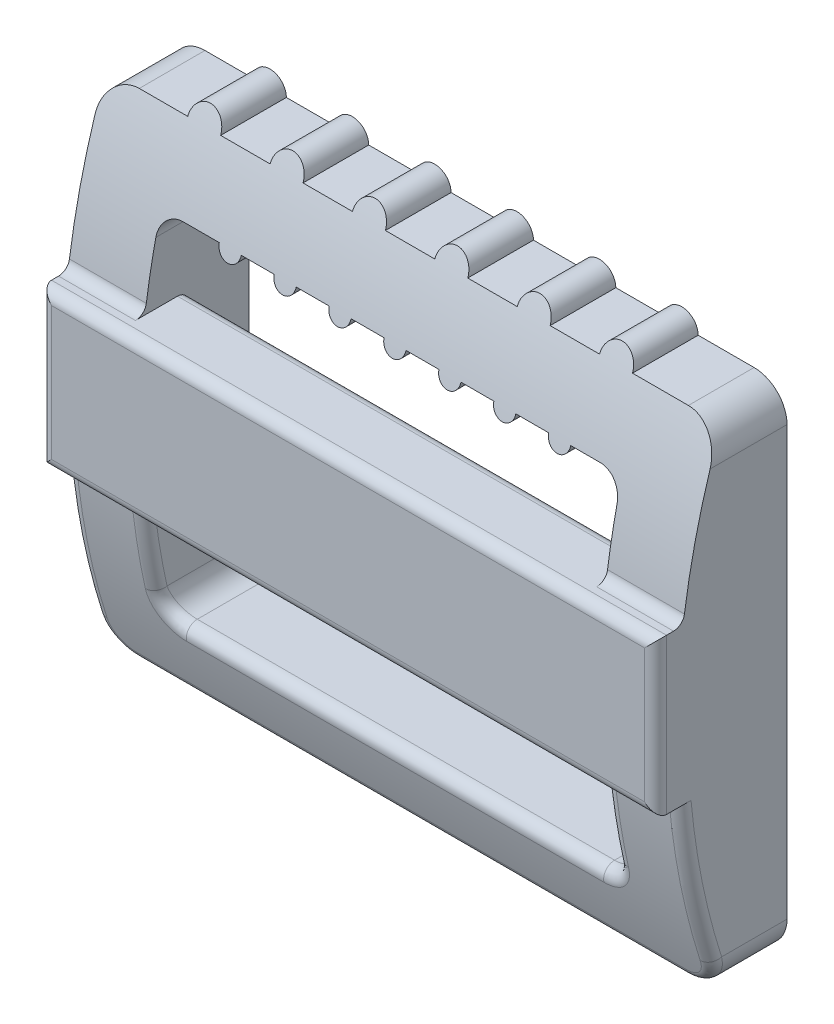
SolidWorks part; units mm, degrees
material "ABS"
ref_plane "Front Plane" through (0, 0, 0) normal (0, 0, 1) x (1, 0, 0)
ref_plane "Top Plane" through (0, 0, 0) normal (0, 1, 0) x (1, 0, 0)
ref_plane "Right Plane" through (0, 0, 0) normal (1, 0, 0) x (0, 0, -1)
sketch "Sketch1" plane through (0, 0, 0) normal (0, 0, 1) x (1, 0, 0)
  line L1 (-25, 22.5) -> (25, 22.5)
  line L2 (-28, 19.5) -> (-28, -19.5)
  line L3 (-25, -22.5) -> (25, -22.5)
  line L4 (28, 19.5) -> (28, -19.5)
  line L5 (-28, 22.5) -> (28, -22.5) construction
  line L6 (-28, -22.5) -> (28, 22.5) construction
  line L7 (-19, 16) -> (19, 16)
  line L8 (-21, 14) -> (-21, -14)
  line L9 (-19, -16) -> (19, -16)
  line L10 (21, 14) -> (21, -14)
  line L11 (-21, 16) -> (21, -16) construction
  line L12 (-21, -16) -> (21, 16) construction
  arc A0 (-28, -19.5) -> (-25, -22.5) centre (-25, -19.5) ccw
  arc A1 (25, -22.5) -> (28, -19.5) centre (25, -19.5) ccw
  arc A2 (25, 22.5) -> (28, 19.5) centre (25, 19.5) cw
  arc A3 (-25, 22.5) -> (-28, 19.5) centre (-25, 19.5) ccw
  arc A4 (-21, -14) -> (-19, -16) centre (-19, -14) ccw
  arc A5 (19, -16) -> (21, -14) centre (19, -14) ccw
  arc A6 (19, 16) -> (21, 14) centre (19, 14) cw
  arc A7 (-19, 16) -> (-21, 14) centre (-19, 14) ccw
  point P0 (0, 0)
  point P18 (0, 0)
  dimension "D3" = 3
  dimension "D6" = 2
  dimension "D1" = 56
  dimension "D2" = 45
  dimension "D4" = 32
  dimension "D5" = 42
extrude "Boss-Extrude1" add sketch "Sketch1" along normal blind 10
sketch "Sketch3" plane through (0, 0, 0) normal (0, 0, 1) x (1, 0, 0)
  line L0 (25, 22.5) -> (-25, 22.5) construction
  circle A0 centre (-19.0901, 22.5) radius 1.5
  dimension "D1" = 3
extrude "Boss-Extrude2" add sketch "Sketch3" along normal blind 10
sketch "Sketch5" plane through (0, 0, 0) normal (0, 0, 1) x (1, 0, 0)
  line L0 (19, 16) -> (-19, 16) construction
  circle A0 centre (-14.6928, 16) radius 1
  dimension "D1" = 2
extrude "Boss-Extrude3" add sketch "Sketch5" along normal blind 10
pattern_linear "LPattern1" count 6 spacing 7.5 along (1, 0, 0) of "Boss-Extrude2"
pattern_linear "LPattern2" count 7 spacing 5 along (1, 0, 0) of "Boss-Extrude3"
sketch "Sketch2" plane through (0, 0, 0) normal (1, 0, 0) x (0, 0, -1)
  circle A0 centre (55, 0) radius 65
  dimension "D2" = 130
  dimension "D1" = 55
extrude "Cut-Extrude2" cut sketch "Sketch2" along normal through all both and the other way through all flip side to cut
sketch "Sketch6" plane through (0, 0, 0) normal (1, 0, 0) x (0, 0, -1)
  line L0 (0, 0) -> (0, -5.7627)
  line L1 (0, -5.7627) -> (-11.9735, -5.7627)
  line L2 (-11.9735, -5.7627) -> (-11.9735, 8.3733)
  line L3 (-11.9735, 8.3733) -> (-5.9868, 8.3733)
  line L4 (-5.9868, 8.3733) -> (0, 0)
extrude "Boss-Extrude4" add sketch "Sketch6" along normal mid plane 56
fillet "Fillet1" radius 1 22 edges at (-21, -9.8814, 0) (-20.4142, -15.4142, 0) (21, -9.8814, 0) (20.4142, -15.4142, 0) (21, -9.9017, 9.2414) (20.5412, -15.2746, 8.1798) (-21, -9.9017, 9.2414) (-20.2215, -15.5837, 8.1043) (27.2787, -21.4512, 6.3583) (0, -22.5, 5.9816) (-26.7904, -21.9072, 6.197) (0, -16, 0) (0, -16, 8) (0, 8.3733, 11.9735) (28, 1.3053, 11.9735) (0, -5.7627, 11.9735) (-28, 1.3053, 11.9735) (-24.5, 8.3733, 9.4584) (24.5, 8.3733, 9.4584) (0, 8.3733, 5.9868) (28, -12.7053, 8.7462) (-28, -12.7053, 8.7462)
sketch "Sketch7" plane through (0, 0, 0) normal (1, 0, 0) x (0, 0, -1)
  line L0 (0.0599, 11.7217) -> (-6.6709, 11.7217)
  line L1 (-6.6709, 11.7217) -> (2.0687, 22.7714)
  line L2 (2.0687, 22.7714) -> (0.0599, 11.7217)
extrude "Cut-Extrude3" cut sketch "Sketch7" against normal mid plane 42
